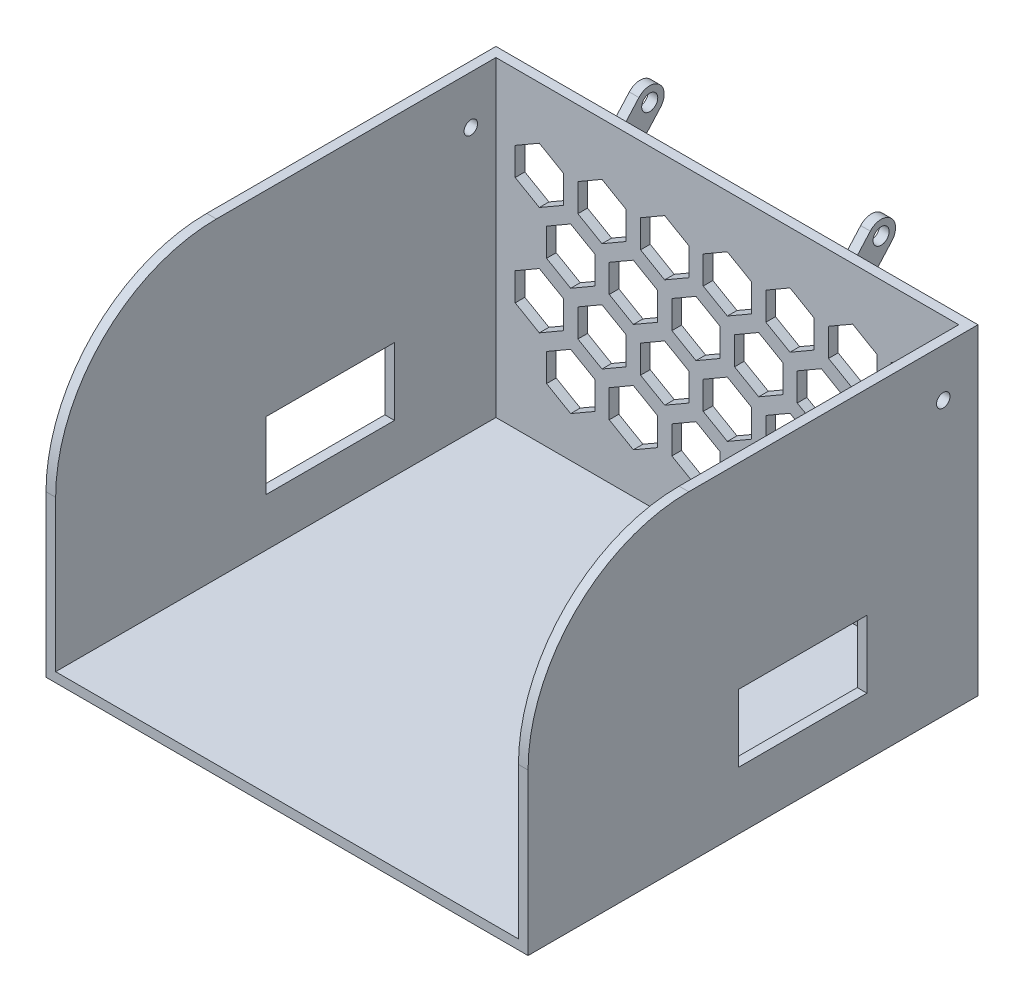
SolidWorks part; units mm, degrees
material "PLA"
ref_plane "Front Plane" through (0, 0, 0) normal (0, 0, 1) x (1, 0, 0)
ref_plane "Top Plane" through (0, 0, 0) normal (0, 1, 0) x (1, 0, 0)
ref_plane "Right Plane" through (0, 0, 0) normal (1, 0, 0) x (0, 0, -1)
sketch "Sketch1" plane through (0, 0, 0) normal (1, 0, 0) x (0, 0, -1)
  line L0 (0, 0) -> (-140, 0)
  line L1 (-140, 0) -> (-140, 50)
  line L2 (-90, 100) -> (0, 100)
  line L3 (0, 100) -> (0, 0)
  arc A0 (-140, 50) -> (-90, 100) centre (-90, 50) cw
  dimension "D1" = 140
  dimension "D2" = 100
  dimension "D3" = 50
extrude "Boss-Extrude1" add sketch "Sketch1" along normal blind 150 contours A0 L2 L3 L0 L1
sketch "Sketch2" plane through (0, 100, 0) normal (0, 1, 0) x (1, 0, 0)
  line L0 (150, 0) -> (0, 0) construction
  line L1 (3, -3) -> (147, -3)
  line L2 (3, -3) -> (3, -145)
  line L3 (3, -145) -> (147, -145)
  line L4 (147, -3) -> (147, -145)
  line L5 (150, -90) -> (150, 0) construction
  line L6 (0, -90) -> (0, 0) construction
  line L8 (150, -140) -> (0, -140) construction
  dimension "D1" = 3
  dimension "D2" = 3
  dimension "D3" = 3
  dimension "D4" = 5
extrude "Cut-Extrude1" cut sketch "Sketch2" against normal offset from surface (97 mm away) 3 up to face at (75, 0, 70)
ref_plane "Plane1" through (75, 0, 0) normal (1, 0, 0) x (0, 0, -1)
ref_plane "Plane2" through (111, 0, 0) normal (1, 0, 0) x (0, 0, -1)
ref_plane "Plane3" through (39, 0, 0) normal (1, 0, 0) x (0, 0, -1)
sketch "Sketch3" plane through (111, 0, 0) normal (1, 0, 0) x (0, 0, -1)
  line L0 (0, 100) -> (0, 86.4837)
  line L1 (0, 86.4837) -> (10.7098, 98.4837)
  line L2 (3.9952, 104.4764) -> (0, 100)
  arc A0 (10.7098, 98.4837) -> (3.9952, 104.4764) centre (7.3525, 101.4801) ccw
  circle A1 centre (7.3525, 101.4801) radius 2.5
  dimension "D1" = 2
  dimension "D2" = 5
  dimension "D3" = 6
  dimension "D4" = 12
extrude "Boss-Extrude2" add sketch "Sketch3" along normal mid plane 3
mirror "Mirror1" about plane through (75, 0, 0) normal (1, 0, 0) of "Boss-Extrude2"
sketch "Sketch4" plane through (150, 0, 0) normal (1, 0, 0) x (0, 0, -1)
  line L0 (-10.8107, 85.0634) -> (-67.3793, 28.4949) construction
  line L1 (-74.5612, 38.9949) -> (-74.5612, 17.9949)
  line L2 (-74.5612, 17.9949) -> (-34.5612, 17.9949)
  line L3 (0, 0) -> (-140, 0) construction
  line L4 (-34.5612, 17.9949) -> (-34.5612, 38.9949)
  line L5 (-34.5612, 38.9949) -> (-74.5612, 38.9949)
  circle A0 centre (-67.3793, 28.4949) radius 2.5
  circle A1 centre (-10.8107, 85.0634) radius 2.1
  point P8 (-74.5612, 28.4949)
  dimension "D4" = 4.2
  dimension "D5" = 5
  dimension "D1" = 80
  dimension "D2" = 45
  dimension "D3" = 40
  dimension "D6" = 21
extrude "Cut-Extrude2" cut sketch "Sketch4" against normal up to next contours A0 | A1 | L4 L5 A0 L1 L2 region at (150, 28.4949, 54.2544) region at (150, 28.4949, 67.3793) region at (150, 85.0634, 10.8107)
mirror "Mirror2" about plane through (75, 0, 0) normal (1, 0, 0) of "Cut-Extrude2"
sketch "Sketch5" plane through (0, 0, 0) normal (0, 0, -1) x (-1, 0, 0)
  line L0 (-150, 75) -> (0, 75) construction
  line L1 (-150, 100) -> (-150, 0) construction
  line L2 (0, 100) -> (0, 0) construction
  line L3 (-75, 100) -> (-75, 0) construction
  line L4 (-109.5, 100) -> (-40.5, 100) construction
  line L5 (-75, 91.3518) -> (-75, -91.3518) construction
  line L6 (-114, 83.6603) -> (-121.5, 79.3301)
  line L7 (-133.5, 83.6603) -> (-141, 79.3301)
  line L8 (-141, 79.3301) -> (-141, 70.6699)
  line L9 (-141, 70.6699) -> (-133.5, 66.3397)
  line L10 (-133.5, 66.3397) -> (-126, 70.6699)
  line L11 (-126, 70.6699) -> (-126, 79.3301)
  line L12 (-126, 79.3301) -> (-133.5, 83.6603)
  line L13 (-121.5, 79.3301) -> (-121.5, 70.6699)
  line L14 (-121.5, 70.6699) -> (-114, 66.3397)
  line L15 (-114, 66.3397) -> (-106.5, 70.6699)
  line L16 (-106.5, 70.6699) -> (-106.5, 79.3301)
  line L17 (-106.5, 79.3301) -> (-114, 83.6603)
  line L18 (-94.5, 83.6603) -> (-102, 79.3301)
  line L19 (-102, 79.3301) -> (-102, 70.6699)
  line L20 (-102, 70.6699) -> (-94.5, 66.3397)
  line L21 (-94.5, 66.3397) -> (-87, 70.6699)
  line L22 (-87, 70.6699) -> (-87, 79.3301)
  line L23 (-87, 79.3301) -> (-94.5, 83.6603)
  line L24 (-75, 83.6603) -> (-82.5, 79.3301)
  line L25 (-82.5, 79.3301) -> (-82.5, 70.6699)
  line L26 (-82.5, 70.6699) -> (-75, 66.3397)
  line L27 (-75, 66.3397) -> (-67.5, 70.6699)
  line L28 (-67.5, 70.6699) -> (-67.5, 79.3301)
  line L29 (-67.5, 79.3301) -> (-75, 83.6603)
  line L30 (-55.5, 83.6603) -> (-63, 79.3301)
  line L31 (-63, 79.3301) -> (-63, 70.6699)
  line L32 (-63, 70.6699) -> (-55.5, 66.3397)
  line L33 (-55.5, 66.3397) -> (-48, 70.6699)
  line L34 (-48, 70.6699) -> (-48, 79.3301)
  line L35 (-48, 79.3301) -> (-55.5, 83.6603)
  line L36 (-36, 83.6603) -> (-43.5, 79.3301)
  line L37 (-43.5, 79.3301) -> (-43.5, 70.6699)
  line L38 (-43.5, 70.6699) -> (-36, 66.3397)
  line L39 (-36, 66.3397) -> (-28.5, 70.6699)
  line L40 (-28.5, 70.6699) -> (-28.5, 79.3301)
  line L41 (-28.5, 79.3301) -> (-36, 83.6603)
  line L42 (-16.5, 83.6603) -> (-24, 79.3301)
  line L43 (-24, 79.3301) -> (-24, 70.6699)
  line L44 (-24, 70.6699) -> (-16.5, 66.3397)
  line L45 (-16.5, 66.3397) -> (-9, 70.6699)
  line L46 (-9, 70.6699) -> (-9, 79.3301)
  line L47 (-9, 79.3301) -> (-16.5, 83.6603)
  line L48 (-150, 58.1125) -> (0, 58.1125) construction
  line L49 (-123.75, 58.1125) -> (-123.75, 75) construction
  line L50 (-123.75, 66.7728) -> (-131.25, 62.4426)
  line L51 (-131.25, 62.4426) -> (-131.25, 53.7824)
  line L52 (-131.25, 53.7824) -> (-123.75, 49.4523)
  line L53 (-123.75, 49.4523) -> (-116.25, 53.7824)
  line L54 (-116.25, 53.7824) -> (-116.25, 62.4426)
  line L55 (-116.25, 62.4426) -> (-123.75, 66.7728)
  line L56 (-37.5, 100) -> (0, 100) construction
  line L57 (-104.25, 66.7728) -> (-111.75, 62.4426)
  line L58 (-111.75, 62.4426) -> (-111.75, 53.7824)
  line L59 (-111.75, 53.7824) -> (-104.25, 49.4523)
  line L60 (-104.25, 49.4523) -> (-96.75, 53.7824)
  line L61 (-96.75, 53.7824) -> (-96.75, 62.4426)
  line L62 (-96.75, 62.4426) -> (-104.25, 66.7728)
  line L63 (-84.75, 66.7728) -> (-92.25, 62.4426)
  line L64 (-92.25, 62.4426) -> (-92.25, 53.7824)
  line L65 (-92.25, 53.7824) -> (-84.75, 49.4523)
  line L66 (-84.75, 49.4523) -> (-77.25, 53.7824)
  line L67 (-77.25, 53.7824) -> (-77.25, 62.4426)
  line L68 (-77.25, 62.4426) -> (-84.75, 66.7728)
  line L69 (-65.25, 66.7728) -> (-72.75, 62.4426)
  line L70 (-72.75, 62.4426) -> (-72.75, 53.7824)
  line L71 (-72.75, 53.7824) -> (-65.25, 49.4523)
  line L72 (-65.25, 49.4523) -> (-57.75, 53.7824)
  line L73 (-57.75, 53.7824) -> (-57.75, 62.4426)
  line L74 (-57.75, 62.4426) -> (-65.25, 66.7728)
  line L75 (-45.75, 66.7728) -> (-53.25, 62.4426)
  line L76 (-53.25, 62.4426) -> (-53.25, 53.7824)
  line L77 (-53.25, 53.7824) -> (-45.75, 49.4523)
  line L78 (-45.75, 49.4523) -> (-38.25, 53.7824)
  line L79 (-38.25, 53.7824) -> (-38.25, 62.4426)
  line L80 (-38.25, 62.4426) -> (-45.75, 66.7728)
  line L81 (-26.25, 66.7728) -> (-33.75, 62.4426)
  line L82 (-33.75, 62.4426) -> (-33.75, 53.7824)
  line L83 (-33.75, 53.7824) -> (-26.25, 49.4523)
  line L84 (-26.25, 49.4523) -> (-18.75, 53.7824)
  line L85 (-18.75, 53.7824) -> (-18.75, 62.4426)
  line L86 (-18.75, 62.4426) -> (-26.25, 66.7728)
  line L87 (-9, 36.8949) -> (-16.5, 32.5648)
  line L88 (-9, 45.5551) -> (-9, 36.8949)
  line L89 (-16.5, 49.8853) -> (-9, 45.5551)
  line L90 (-24, 45.5551) -> (-16.5, 49.8853)
  line L91 (-24, 36.8949) -> (-24, 45.5551)
  line L92 (-16.5, 32.5648) -> (-24, 36.8949)
  line L93 (-28.5, 36.8949) -> (-36, 32.5648)
  line L94 (-28.5, 45.5551) -> (-28.5, 36.8949)
  line L95 (-36, 49.8853) -> (-28.5, 45.5551)
  line L96 (-43.5, 45.5551) -> (-36, 49.8853)
  line L97 (-43.5, 36.8949) -> (-43.5, 45.5551)
  line L98 (-36, 32.5648) -> (-43.5, 36.8949)
  line L99 (-48, 36.8949) -> (-55.5, 32.5648)
  line L100 (-48, 45.5551) -> (-48, 36.8949)
  line L101 (-55.5, 49.8853) -> (-48, 45.5551)
  line L102 (-63, 45.5551) -> (-55.5, 49.8853)
  line L103 (-63, 36.8949) -> (-63, 45.5551)
  line L104 (-55.5, 32.5648) -> (-63, 36.8949)
  line L105 (-67.5, 36.8949) -> (-75, 32.5648)
  line L106 (-67.5, 45.5551) -> (-67.5, 36.8949)
  line L107 (-75, 49.8853) -> (-67.5, 45.5551)
  line L108 (-82.5, 45.5551) -> (-75, 49.8853)
  line L109 (-82.5, 36.8949) -> (-82.5, 45.5551)
  line L110 (-75, 32.5648) -> (-82.5, 36.8949)
  line L111 (-87, 36.8949) -> (-94.5, 32.5648)
  line L112 (-87, 45.5551) -> (-87, 36.8949)
  line L113 (-94.5, 49.8853) -> (-87, 45.5551)
  line L114 (-102, 45.5551) -> (-94.5, 49.8853)
  line L115 (-102, 36.8949) -> (-102, 45.5551)
  line L116 (-94.5, 32.5648) -> (-102, 36.8949)
  line L117 (-106.5, 36.8949) -> (-114, 32.5648)
  line L118 (-106.5, 45.5551) -> (-106.5, 36.8949)
  line L119 (-114, 49.8853) -> (-106.5, 45.5551)
  line L120 (-121.5, 45.5551) -> (-114, 49.8853)
  line L121 (-121.5, 36.8949) -> (-121.5, 45.5551)
  line L122 (-114, 32.5648) -> (-121.5, 36.8949)
  line L123 (-126, 36.8949) -> (-133.5, 32.5648)
  line L124 (-126, 45.5551) -> (-126, 36.8949)
  line L125 (-133.5, 49.8853) -> (-126, 45.5551)
  line L126 (-141, 45.5551) -> (-133.5, 49.8853)
  line L127 (-141, 36.8949) -> (-141, 45.5551)
  line L128 (-133.5, 32.5648) -> (-141, 36.8949)
  line L129 (-141, 41.225) -> (-9, 41.225) construction
  line L130 (-18.75, 20.0074) -> (-26.25, 15.6773)
  line L131 (-18.75, 28.6676) -> (-18.75, 20.0074)
  line L132 (-26.25, 32.9978) -> (-18.75, 28.6676)
  line L133 (-33.75, 28.6676) -> (-26.25, 32.9978)
  line L134 (-33.75, 20.0074) -> (-33.75, 28.6676)
  line L135 (-26.25, 15.6773) -> (-33.75, 20.0074)
  line L136 (-38.25, 20.0074) -> (-45.75, 15.6773)
  line L137 (-38.25, 28.6676) -> (-38.25, 20.0074)
  line L138 (-45.75, 32.9978) -> (-38.25, 28.6676)
  line L139 (-53.25, 28.6676) -> (-45.75, 32.9978)
  line L140 (-53.25, 20.0074) -> (-53.25, 28.6676)
  line L141 (-45.75, 15.6773) -> (-53.25, 20.0074)
  line L142 (-57.75, 20.0074) -> (-65.25, 15.6773)
  line L143 (-57.75, 28.6676) -> (-57.75, 20.0074)
  line L144 (-65.25, 32.9978) -> (-57.75, 28.6676)
  line L145 (-72.75, 28.6676) -> (-65.25, 32.9978)
  line L146 (-72.75, 20.0074) -> (-72.75, 28.6676)
  line L147 (-65.25, 15.6773) -> (-72.75, 20.0074)
  line L148 (-77.25, 20.0074) -> (-84.75, 15.6773)
  line L149 (-77.25, 28.6676) -> (-77.25, 20.0074)
  line L150 (-84.75, 32.9978) -> (-77.25, 28.6676)
  line L151 (-92.25, 28.6676) -> (-84.75, 32.9978)
  line L152 (-92.25, 20.0074) -> (-92.25, 28.6676)
  line L153 (-84.75, 15.6773) -> (-92.25, 20.0074)
  line L154 (-96.75, 20.0074) -> (-104.25, 15.6773)
  line L155 (-96.75, 28.6676) -> (-96.75, 20.0074)
  line L156 (-104.25, 32.9978) -> (-96.75, 28.6676)
  line L157 (-111.75, 28.6676) -> (-104.25, 32.9978)
  line L158 (-111.75, 20.0074) -> (-111.75, 28.6676)
  line L159 (-104.25, 15.6773) -> (-111.75, 20.0074)
  line L160 (-116.25, 20.0074) -> (-123.75, 15.6773)
  line L161 (-116.25, 28.6676) -> (-116.25, 20.0074)
  line L162 (-123.75, 32.9978) -> (-116.25, 28.6676)
  line L163 (-131.25, 28.6676) -> (-123.75, 32.9978)
  line L164 (-131.25, 20.0074) -> (-131.25, 28.6676)
  line L165 (-123.75, 15.6773) -> (-131.25, 20.0074)
  circle A0 centre (-133.5, 75) radius 7.5 construction
  circle A1 centre (-123.75, 58.1125) radius 7.5 construction
  point P71 (-120, 64.6077)
  point P72 (-117.75, 68.5048)
  dimension "D2" = 15
  dimension "D3" = 9
  dimension "D4" = 9
  dimension "D5" = 25
  dimension "D6" = 4.5
  dimension "D8" = 18.75
  dimension "D1" = 7
  dimension "D7" = 6
extrude "Cut-Extrude3" cut sketch "Sketch5" against normal blind 10
equation "\"forward_length\"= 130"
equation "\"height\"= 100"
equation "\"eslabon_AB\"=80"
